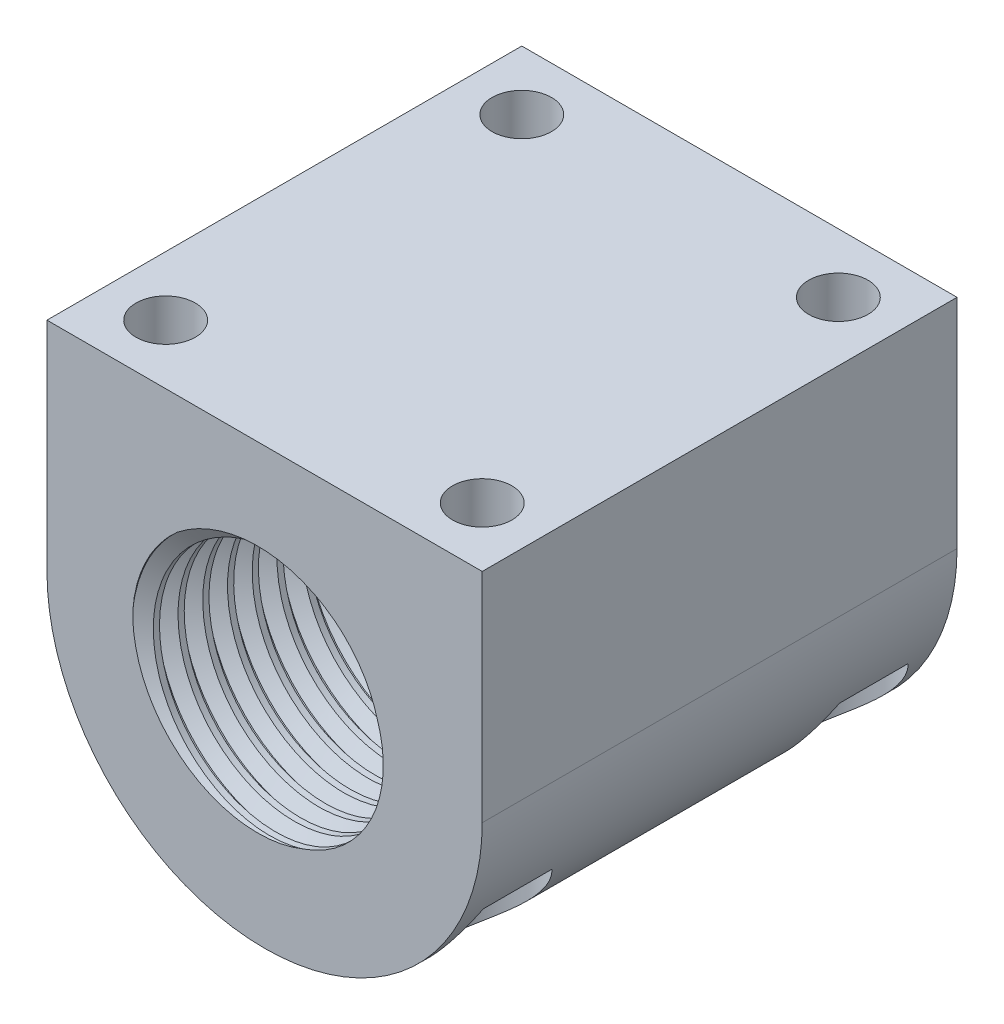
SolidWorks part; units mm, degrees
ref_plane "Front" through (0, 0, 0) normal (0, 0, 1) x (1, 0, 0)
ref_plane "Top" through (0, 0, 0) normal (0, 1, 0) x (1, 0, 0)
ref_plane "Right" through (0, 0, 0) normal (1, 0, 0) x (0, 0, -1)
sketch "Esquisse1" plane through (0, 0, 0) normal (0, 0, 1) x (1, 0, 0)
  line L0 (-11, 0) -> (-11, 11)
  line L1 (-11, 11) -> (11, 11)
  line L2 (11, 11) -> (11, 0)
  circle A0 centre (0, 0) radius 11
  circle A1 centre (0, 0) radius 6
  dimension "D1" = 22
  dimension "D2" = 12
extrude "Boss.-Extru.1" add sketch "Esquisse1" along normal blind 24 contours A0 L1 L0 | A0 L2 L1 | A0 A1 region at (-7.5582, 7.5582, 0) region at (-8.543, 8.543, 0) region at (8.543, 8.543, 0)
thread "Filetage1" pitch 1.25 method cut profile "Profil de filetage1" start angle 1, offset 2, length 0, pitch 1.25, diameter 12
ref_plane "Plan1" through (5.9991, 0.1047, -2) normal (0.0175, -0.9998, 0) x (0.9998, 0.0175, 0)
sketch "Profil de filetage1" plane through (5.9991, 0.1047, -2) normal (0.0175, -0.9998, 0) x (0.9998, 0.0175, 0)
  line L0 (0, 0) -> (0, 1.25) construction
  line L1 (0, 0) -> (0.6766, 0.3906)
  line L2 (0.6766, 0.3906) -> (0.6766, 0.5469)
  line L3 (0.6766, 0.5469) -> (0, 0.9375)
  line L4 (0.6766, 0.4687) -> (0, 0.4687) construction
  line L11 (0, 0) -> (0, 0.9375)
  point P2 (0, 0)
  dimension "Pitch" = 1.25
  dimension "Profile_Angle" = 60
  dimension "Profile_Land" = 0.1562
  dimension "Profile_Height" = 0.6766
sketch "Esquisse5" plane through (0, 11, 0) normal (0, 1, 0) x (1, 0, 0)
  line L0 (-11, -24) -> (-11, 0) construction
  line L1 (-11, 0) -> (11, 0) construction
  circle A0 centre (-8, -3) radius 1.5
  circle A1 centre (-8, -3) radius 2.5
  circle A2 centre (8, -3) radius 2.5
  circle A3 centre (8, -3) radius 1.5
  circle A4 centre (8, -21) radius 2.5
  circle A5 centre (8, -21) radius 1.5
  circle A6 centre (-8, -21) radius 2.5
  circle A7 centre (-8, -21) radius 1.5
  dimension "D1" = 3
  dimension "D2" = 3
  dimension "D3" = 3
  dimension "D4" = 5
  dimension "D5" = 2
  dimension "D6" = 2
extrude "Enlèv. mat.-Extru.1" cut sketch "Esquisse5" against normal through all contours A7 | A5 | A3 | A0 | A0 region at (-8, 11, 3) region at (8, 11, 3) region at (8, 11, 21) region at (-8, 11, 21)
extrude "Enlèv. mat.-Extru.2" cut sketch "Esquisse5<3>" against normal blind 5 from offset 16 offset against normal yes
sketch "Esquisse5<3>" plane through (0, 11, 0) normal (0, 1, 0) x (1, 0, 0) same geometry as "Esquisse5"
